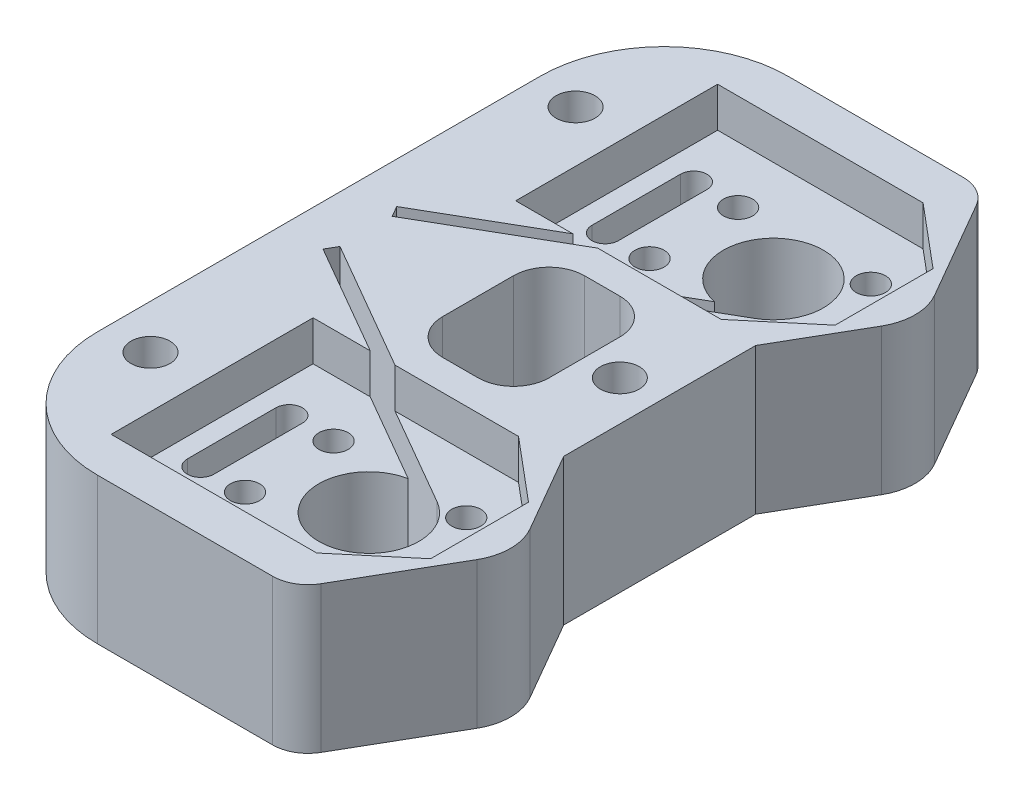
SolidWorks part; units mm, degrees
note: The reader was unsure of these and kept them because the rebuilt part matched: shared geometry of "Sketch11<4>".
material "Acrylic (Medium-high impact)"
ref_plane "Front Plane" through (0, 0, 0) normal (0, 0, 1) x (1, 0, 0)
ref_plane "Top Plane" through (0, 0, 0) normal (0, 1, 0) x (1, 0, 0)
ref_plane "Right Plane" through (0, 0, 0) normal (1, 0, 0) x (0, 0, -1)
sketch "Sketch1" plane through (0, 0, 0) normal (0, 1, 0) x (1, 0, 0)
  line L0 (32.3833, 19.5) -> (1.2064, 19.5)
  line L1 (1.2064, -19.5) -> (32.3833, -19.5)
  line L3 (21.125, 36.5896) -> (17.5, 30.3109) construction
  line L4 (0, 0) -> (17.5, -30.3109) construction
  line L5 (19.3833, -4) -> (25.3833, -4)
  line L6 (10.3833, 19.5) -> (10.3833, -19.5)
  line L7 (9.8667, 43.0896) -> (32.3833, 30.0896)
  line L9 (9.7058, 34.8109) -> (25.2942, 25.8109) construction
  line L10 (25.2942, -25.8109) -> (9.7058, -34.8109) construction
  line L11 (1.2064, 25.305) -> (1.2064, -25.305)
  line L12 (17.5, 30.3109) -> (0, 0) construction
  line L13 (19.3833, -4) -> (19.3833, 4)
  line L14 (19.3833, 4) -> (25.3833, 4)
  line L15 (0, 0) -> (26.3833, 0) construction
  line L16 (32.3833, 30.0896) -> (32.3833, -30.0896)
  line L17 (32.3833, -30.0896) -> (9.8667, -43.0896)
  line L18 (25.3833, -4) -> (25.3833, 4)
  line L19 (19.3833, -4) -> (25.3833, 4) construction
  line L20 (19.3833, 4) -> (25.3833, -4) construction
  line L23 (9.8667, 43.0896) -> (1.2064, 38.0896)
  line L24 (9.8667, -43.0896) -> (1.2064, -38.0896)
  line L25 (1.2064, 38.0896) -> (1.2064, 25.305)
  line L28 (1.2064, -38.0896) -> (1.2064, -25.305)
  line L35 (14.4288, 36.9915) -> (24.8212, 30.9915) construction
  line L69 (5.2064, -28.305) -> (5.2064, 0) construction
  line L70 (5.2064, 0) -> (5.2064, 28.305) construction
  point P4 (22.3833, 0)
  point P85 (0, 0)
  point P92 (13.1917, 0)
  point P93 (0, 0)
  point P148 (0, 0)
  dimension "D7" = 6
  dimension "D9" = 26
  dimension "D8" = 8
  dimension "D11" = 35
  dimension "D10" = 10
  dimension "D1" = 18
  dimension "D3" = 7.25
  dimension "D4" = 120
  dimension "D5" = 39
  dimension "D6" = 22
  dimension "D15" = 10
  dimension "D18" = 12
  dimension "D22" = 42.25
extrude "Boss-Extrude1" add sketch "Sketch1" along normal blind 8.25
sketch "Sketch8" plane through (0, 8.25, 0) normal (0, 1, 0) x (1, 0, 0)
  line L1 (15.7833, 17.1207) -> (27.3833, 17.1207)
  line L2 (15.7833, 17.1207) -> (15.7833, 5.7207)
  line L3 (15.7833, 5.7207) -> (27.3833, 5.7207)
  line L4 (30.8833, 14.1838) -> (30.8833, 8.6575)
  line L5 (32.3833, 19.5) -> (32.3833, -19.5) construction
  line L6 (32.3833, 0) -> (10.3833, 0) construction
  line L7 (10.3833, 19.5) -> (10.3833, -19.5) construction
  line L11 (27.3833, 5.7207) -> (30.8833, 8.6575)
  line L12 (27.3833, 17.1207) -> (30.8833, 14.1838)
  line L14 (32.3833, 19.5) -> (32.3833, -19.5) construction
  line L16 (27.3833, -17.1207) -> (30.8833, -14.1838)
  line L17 (27.3833, -5.7207) -> (30.8833, -8.6575)
  line L18 (30.8833, -14.1838) -> (30.8833, -8.6575)
  line L19 (15.7833, -5.7207) -> (27.3833, -5.7207)
  line L20 (15.7833, -17.1207) -> (15.7833, -5.7207)
  line L21 (15.7833, -17.1207) -> (27.3833, -17.1207)
  point P1 (30.8833, 5.7207)
  point P3 (30.8833, 17.1207)
  point P22 (30.8833, -17.1207)
  point P23 (30.8833, -5.7207)
  point P24 (30.4571, -17.1207)
  dimension "D5" = 40
  dimension "D1" = 11.4
  dimension "D2" = 15.1
  dimension "D3" = 1.5
  dimension "D4" = 3.5
  dimension "D6" = 3.5
  dimension "D7" = 40
extrude "Cut-Extrude3" cut sketch "Sketch8" against normal blind 2.25
sketch "Sketch7" plane through (0, 6, 0) normal (0, 1, 0) x (1, 0, 0)
  line L0 (15.7833, 17.1207) -> (15.7833, 5.7207) construction
  line L1 (32.3833, 19.5) -> (32.3833, -19.5) construction
  line L4 (19.1333, 11.4207) -> (12.4333, 11.4207) construction
  line L5 (32.3833, 0) -> (10.3833, 0) construction
  line L7 (10.3833, 19.5) -> (10.3833, -19.5) construction
  line L8 (30.8833, 8.6575) -> (30.8833, 14.1838) construction
  circle A0 centre (24.6333, 11.4207) radius 2.825
  circle A13 centre (20.1403, 13.9207) radius 0.825
  circle A14 centre (27.6333, 13.9207) radius 0.825
  circle A15 centre (27.6333, 8.9207) radius 0.825
  circle A16 centre (20.1403, 8.9207) radius 0.825
  circle A17 centre (20.1403, -8.9207) radius 0.825
  circle A18 centre (27.6333, -8.9207) radius 0.825
  circle A19 centre (27.6333, -13.9207) radius 0.825
  circle A20 centre (20.1403, -13.9207) radius 0.825
  circle A21 centre (24.6333, -11.4207) radius 2.825
  point P30 (15.7833, 11.4207)
  dimension "D1" = 5.65
  dimension "D2" = 1.65
  dimension "D3" = 2
  dimension "D4" = 2
  dimension "D5" = 3
  dimension "D6" = 2.5
  dimension "D7" = 6.25
extrude "Cut-Extrude4" cut sketch "Sketch7" against normal blind 1.25
sketch "Sketch9" plane through (0, 6, 0) normal (0, 1, 0) x (1, 0, 0)
  line L0 (30.8833, 8.6575) -> (30.8833, 14.1838) construction
  line L1 (32.3833, 0) -> (10.3833, 0) construction
  line L2 (32.3833, 19.5) -> (32.3833, -19.5) construction
  line L3 (10.3833, 19.5) -> (10.3833, -19.5) construction
  line L4 (17.6333, 8.9207) -> (17.6333, 13.9207) construction
  line L7 (17.6333, -8.9207) -> (17.6333, -13.9207) construction
  line L10 (16.8833, 8.9207) -> (16.8833, 13.9207)
  line L11 (18.3833, 8.9207) -> (18.3833, 13.9207)
  line L12 (15.7833, 17.1207) -> (15.7833, 5.7207) construction
  line L13 (16.8833, -8.9207) -> (16.8833, -13.9207)
  line L14 (18.3833, -8.9207) -> (18.3833, -13.9207)
  arc A1 (16.8833, -8.9207) -> (18.3833, -8.9207) centre (17.6333, -8.9207) cw
  arc A3 (18.3833, -13.9207) -> (16.8833, -13.9207) centre (17.6333, -13.9207) cw
  circle A6 centre (30.1333, 11.4207) radius 0.75
  circle A7 centre (24.6333, 11.4207) radius 2.825 construction
  circle A13 centre (30.1333, -11.4207) radius 0.75
  arc A19 (16.8833, 8.9207) -> (18.3833, 8.9207) centre (17.6333, 8.9207) ccw
  arc A20 (18.3833, 13.9207) -> (16.8833, 13.9207) centre (17.6333, 13.9207) ccw
  point P2 (17.6333, 11.4207)
  point P9 (0, 0)
  point P16 (30.8833, 11.4207)
  point P27 (17.6333, -11.4207)
  point P31 (15.7833, 11.4207)
  dimension "D1" = 7
  dimension "D2" = 5
  dimension "D3" = 0.75
  dimension "D5" = 1.5
  dimension "D6" = 5.5
extrude "Cut-Extrude5" cut sketch "Sketch9" against normal through all
sketch "Sketch6" plane through (0, 8.25, 0) normal (0, -1, 0) x (-1, 0, 0)
  line L0 (0, 0) -> (32.3833, 0) construction
  line L1 (-26.0458, -8.9742) -> (-25.6958, -9.5804)
  line L2 (-12.7054, -2.0804) -> (-25.6958, -9.5804)
  line L3 (-13.0554, -1.4742) -> (-26.0458, -8.9742)
  line L4 (-13.0554, -1.4742) -> (-12.7054, -2.0804)
  line L5 (-13.0554, 1.4742) -> (-12.7054, 2.0804)
  line L6 (-32.3833, 19.5) -> (-32.3833, -19.5) construction
  line L7 (-13.0554, 1.4742) -> (-26.0458, 8.9742)
  line L8 (-12.7054, 2.0804) -> (-25.6958, 9.5804)
  line L9 (-26.0458, 8.9742) -> (-25.6958, 9.5804)
  circle A0 centre (-24.6333, -11.4207) radius 2.825
  circle A2 centre (-24.6333, 11.4207) radius 2.825
  circle A3 centre (-24.6333, -11.4207) radius 2.825 construction
  dimension "D1" = 5.65
  dimension "D2" = 15
  dimension "D3" = 60
  dimension "D4" = 0.7
extrude "Cut-Extrude1" cut sketch "Sketch6" along normal through all both and the other way through all
sketch "Sketch11" plane through (0, 8.25, 0) normal (0, 1, 0) x (1, 0, 0)
  line L0 (29.6333, 3.8625) -> (29.6333, 22.3095) construction
  line L1 (32.2314, 12.9207) -> (28.4328, 19.5)
  line L2 (32.2314, 9.9207) -> (29.6333, 5.4207)
  line L3 (29.6333, 11.4207) -> (29.6333, 17.4207)
  line L4 (29.6333, 11.4207) -> (29.6333, 5.4207)
  line L5 (32.3833, 0) -> (10.3833, 0) construction
  line L6 (32.3833, 19.5) -> (32.3833, -19.5) construction
  line L7 (10.3833, 19.5) -> (10.3833, -19.5) construction
  line L8 (29.6333, 5.4207) -> (29.6333, -5.4207)
  line L9 (32.3833, -19.5) -> (23.5715, -19.5) construction
  line L10 (29.6333, -3.8625) -> (29.6333, -22.3095) construction
  line L11 (29.6333, -11.4207) -> (29.6333, -5.4207)
  line L12 (29.6333, -11.4207) -> (29.6333, -17.4207)
  line L13 (32.3833, 19.5) -> (23.5715, 19.5) construction
  line L14 (32.3833, 19.5) -> (10.3833, 19.5) construction
  line L15 (32.2314, -9.9207) -> (29.6333, -5.4207)
  line L16 (32.2314, -12.9207) -> (28.4328, -19.5)
  arc A0 (29.6333, 8.4207) -> (29.6333, 14.4207) centre (29.6333, 11.4207) ccw
  arc A1 (26.0458, 8.9742) -> (24.0838, 8.6496) centre (24.6333, 11.4207) ccw construction
  arc A2 (29.6333, -8.4207) -> (29.6333, -14.4207) centre (29.6333, -11.4207) cw
  point P20 (29.6333, 0)
  line M26 (10.3833, -19.5) -> (32.3833, -19.5)
  line M28 (32.3833, -19.5) -> (32.3833, 19.5)
  line M30 (32.3833, 19.5) -> (10.3833, 19.5)
  dimension "D1" = 5
  dimension "D2" = 0
  dimension "D3" = 6
  dimension "D4" = 6
  dimension "D5" = 6
extrude "Boss-Extrude2" add sketch "Sketch11" against normal through all contours A0 M28 | A2 M28
fillet "Fillet4" radius 2 4 edges at (25.3833, 4.125, -4) (19.3833, 4.125, 4) (25.3833, 4.125, 4) (19.3833, 4.125, -4)
extrude "Cut-Extrude7" cut sketch "Sketch11<4>" against normal through all contours A0 L1 M28 M30 | L15 A2 A0 L2 L8 M28 | A2 L16 M28 M26
sketch "Sketch11<4>" plane through (0, 8.25, 0) normal (0, 1, 0) x (1, 0, 0) same geometry as "Sketch11"
fillet "Fillet5" radius 7 2 edges at (10.3833, 4.125, 19.5) (10.3833, 4.125, -19.5)
sketch "Sketch12" plane through (0, 8.25, 0) normal (0, 1, 0) x (1, 0, 0)
  line L0 (12.8833, 12) -> (12.8833, -12) construction
  line L1 (10.3833, 12.5) -> (10.3833, -12.5) construction
  line L2 (12.8833, 0) -> (27.3833, 0) construction
  line L3 (29.6333, 5.4207) -> (29.6333, -5.4207) construction
  point P4 (10.3833, 0)
  point P5 (12.8833, 0)
  dimension "D1" = 24
  dimension "D2" = 14.5
  dimension "D3" = 2.25
hole_wizard "Ø2.2 (2.2) Diameter Hole1" positions "3DSketch1" profile "Sketch13" hole size "Ø2.2" standard "ISO" end condition through all
sketch3d "3DSketch1"
  point P0 (12.8833, 8.25, -12)
  point P3 (27.3833, 8.25, 0)
  point P6 (12.8833, 8.25, 12)
sketch "Sketch13" plane through (12.8833, 8.25, -12) normal (1, 0, 0) x (0, 0, 1)
  line L0 (0, 0) -> (0, 8.25)
  line L1 (0, 8.25) -> (1.1, 8.25)
  line L2 (1.1, 8.25) -> (1.1, 0)
  line L5 (1.1, 0) -> (0, 0)
  line L11 (0, -6.35) -> (0, 107.95) construction
  dimension "Thru Hole Dia." = 2.2
  dimension "Thru Hole Depth" = 8.25
fillet "Fillet6" radius 2 2 edges at (28.4328, 4.125, 19.5) (28.4328, 4.125, -19.5)
